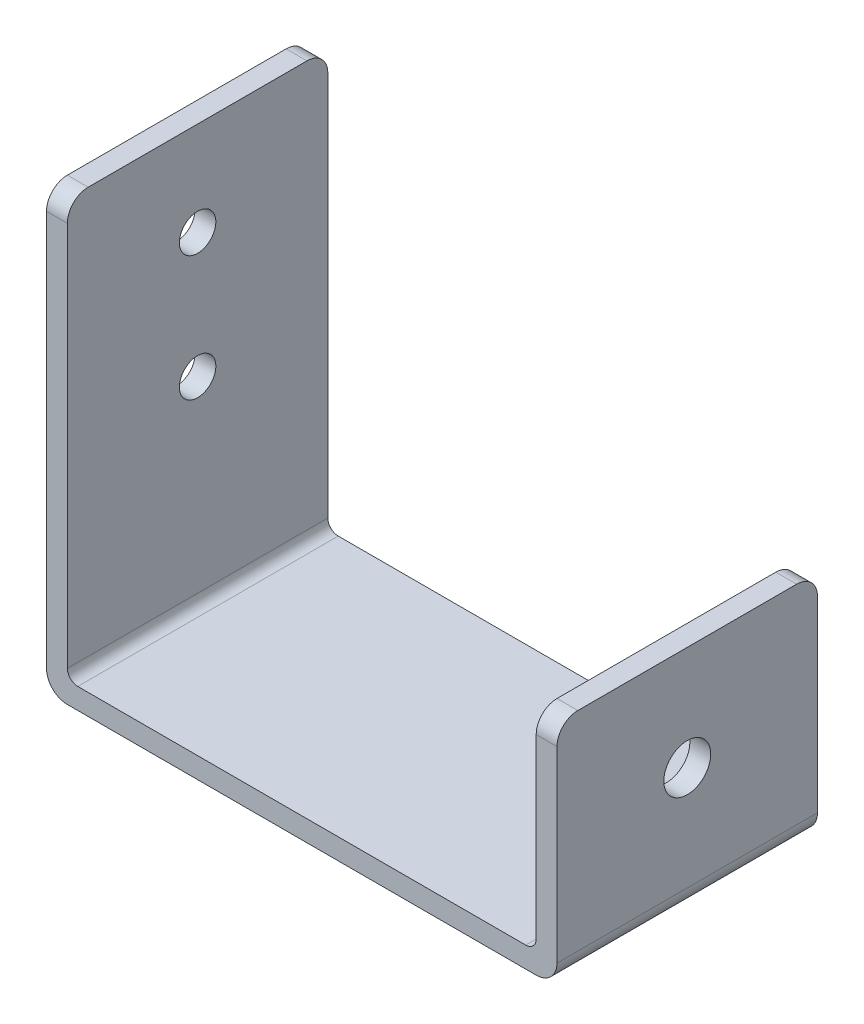
SolidWorks part; units mm, degrees
ref_plane "Plan de face" through (0, 0, 0) normal (0, 0, 1) x (1, 0, 0)
ref_plane "Plan de dessus" through (0, 0, 0) normal (0, 1, 0) x (1, 0, 0)
ref_plane "Plan de droite" through (0, 0, 0) normal (1, 0, 0) x (0, 0, -1)
sketch "Esquisse1" plane through (0, 0, 0) normal (0, 0, 1) x (1, 0, 0)
  line L0 (0, 0) -> (45, 0)
  line L1 (0, 0) -> (0, 40)
  line L2 (45, 0) -> (45, 20)
  dimension "D1" = 45
  dimension "D2" = 20
  dimension "D3" = 40
extrude "Extru.-Mince1" add sketch "Esquisse1" along normal blind 25 thin thin type one direction wall 2
fillet "Congé1" radius 1 1 edges at (0, 0, 12.5)
fillet "Congé2" radius 1 1 edges at (45, 0, 12.5)
fillet "Congé3" radius 2 1 edges at (47, -2, 12.5)
fillet "Congé4" radius 2 1 edges at (-2, -2, 12.5)
sketch "Esquisse2" plane through (-2, 0, 0) normal (-1, 0, 0) x (0, 0, 1)
  line L0 (-4.3852, 25) -> (27.735, 25) construction
  line L1 (12.5, 41.2385) -> (12.5, 10.4299) construction
  line L2 (0, 40) -> (0, 0) construction
  line L3 (25, 40) -> (0, 40) construction
  circle A0 centre (12.5, 31) radius 1.75
  circle A1 centre (12.5, 19) radius 1.75
  dimension "D7" = 3.5
  dimension "D10" = 3.5
  dimension "D1" = 12.5
  dimension "D2" = 15
  dimension "D3" = 6
  dimension "D4" = 6
extrude "Enlèv. mat.-Extru.1" cut sketch "Esquisse2" against normal blind 2
sketch "Esquisse3" plane through (47, 0, 0) normal (1, 0, 0) x (0, 0, -1)
  line L0 (0, -2) -> (-25, -2) construction
  line L1 (-25, 0) -> (-25, 20) construction
  circle A0 centre (-12.5, 10) radius 2.25
  dimension "D1" = 4.5
  dimension "D2" = 12
  dimension "D3" = 12.5
extrude "Enlèv. mat.-Extru.2" cut sketch "Esquisse3" against normal blind 2
fillet "Congé12" radius 2 1 edges at (46, 20, 0)
fillet "Congé13" radius 2 1 edges at (46, 20, 25)
fillet "Congé15" radius 2 1 edges at (-1, 40, 0)
fillet "Congé16" radius 2 1 edges at (-1, 40, 25)
